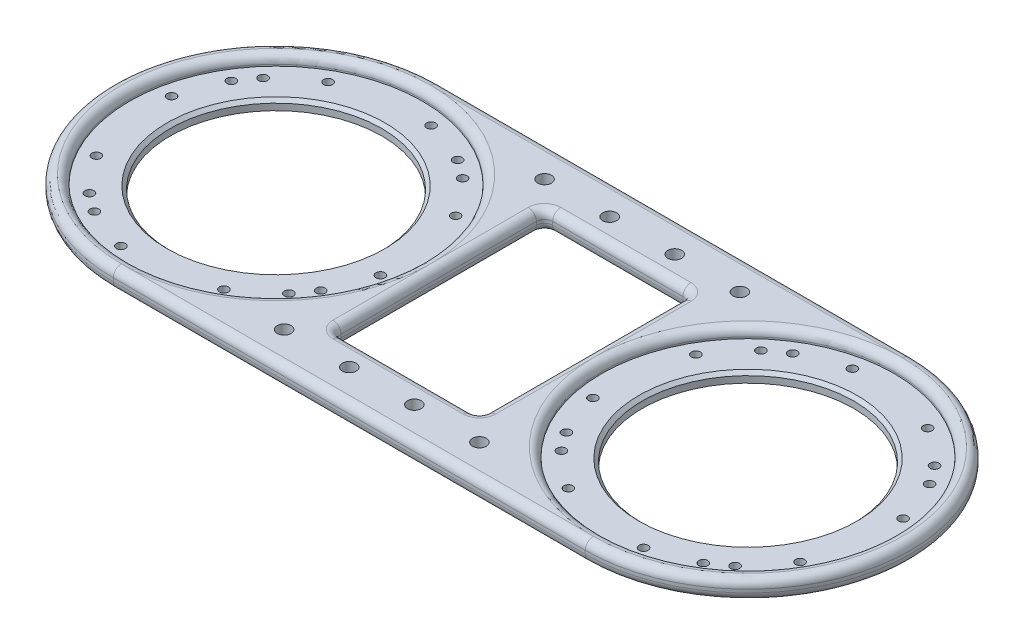
SolidWorks part; units mm, degrees
ref_plane "前视基准面" through (0, 0, 0) normal (0, 0, 1) x (1, 0, 0)
ref_plane "上视基准面" through (0, 0, 0) normal (0, 1, 0) x (1, 0, 0)
ref_plane "右视基准面" through (0, 0, 0) normal (1, 0, 0) x (0, 0, -1)
other "Configuration Table"
sketch "草图1" plane through (0, 0, 0) normal (0, 1, 0) x (1, 0, 0)
  line L0 (-145, 0) -> (145, 0) construction
  line L1 (-145, 100) -> (145, 100)
  line L2 (-145, -100) -> (145, -100)
  arc A0 (-145, 100) -> (-145, -100) centre (-145, 0) ccw
  arc A1 (145, -100) -> (145, 100) centre (145, 0) ccw
  point P3 (0, 0)
  dimension "D1" = 100
  dimension "D2" = 290
extrude "凸台-拉伸1" add sketch "草图1" along normal blind 6 and the other way blind 6
sketch "草图2" plane through (0, 0, 0) normal (0, 0, 1) x (1, 0, 0)
  line L0 (-145, 6) -> (-145, -6) construction
  line L1 (-145, -6) -> (-80, -6)
  line L2 (-145, -6) -> (145, -6) construction
  line L3 (-80, -6) -> (-80, 0)
  line L4 (-80, 0) -> (-55, 0)
  line L5 (-55, 0) -> (-55, 6)
  line L6 (-145, 6) -> (145, 6) construction
  line L7 (-55, 6) -> (-145, 6)
  line L8 (-145, 6) -> (-145, -6)
  dimension "D1" = 130
  dimension "D2" = 180
revolve "切除-旋转1" cut sketch "草图2" angle 360 about L0
sketch "草图3" plane through (0, 0, 0) normal (0, 1, 0) x (1, 0, 0)
  line L0 (-145, 0) -> (-129.4354, 79.7452) construction
  line L1 (-73.8216, 39.1816) -> (-145, 0) construction
  line L2 (-102.9484, 69.5214) -> (-145, 0) construction
  line L3 (-91.648, 61.2791) -> (-145, 0) construction
  line L4 (-145, 0) -> (-145, 81.25) construction
  circle A0 centre (-145, 0) radius 81.25 construction
  circle A1 centre (-102.9484, 69.5214) radius 2.75
  circle A2 centre (-91.648, 61.2791) radius 2.75
  circle A3 centre (-73.8216, 39.1816) radius 2.75
  circle A4 centre (-129.4354, 79.7452) radius 2.75
  circle A5 centre (-145, 0) radius 65 construction
  circle A18 centre (-75.4786, -42.0516) radius 2.75
  circle A19 centre (-83.7209, -53.352) radius 2.75
  circle A20 centre (-105.8184, -71.1784) radius 2.75
  circle A21 centre (-65.2548, -15.5646) radius 2.75
  circle A22 centre (-187.0516, -69.5214) radius 2.75
  circle A23 centre (-198.352, -61.2791) radius 2.75
  circle A24 centre (-216.1784, -39.1816) radius 2.75
  circle A25 centre (-160.5646, -79.7452) radius 2.75
  circle A26 centre (-214.5214, 42.0516) radius 2.75
  circle A27 centre (-206.2791, 53.352) radius 2.75
  circle A28 centre (-184.1816, 71.1784) radius 2.75
  circle A29 centre (-224.7452, 15.5646) radius 2.75
  point P41 (-145, 0)
  dimension "D1" = 162.5
  dimension "D2" = 5.5
  dimension "D3" = 50.124
  dimension "D4" = 20.124
  dimension "D5" = 20.124
  dimension "D6" = 11.044
  dimension "D7" = 4
extrude "切除-拉伸1" cut sketch "草图3" against normal up to next
mirror "镜向1" about plane through (0, 0, 0) normal (1, 0, 0) of "切除-拉伸1", "切除-旋转1"
sketch "草图4" plane through (0, 6, 0) normal (0, 1, 0) x (1, 0, 0)
  line L0 (0, -80) -> (0, -100) construction
  line L1 (-145, -100) -> (145, -100) construction
  line L2 (-64, -100) -> (64, -100)
  arc A0 (0, -80) -> (64, -100) centre (64, 12.4) ccw
  arc A1 (0, -80) -> (-64, -100) centre (-64, 12.4) cw
  dimension "D1" = 20
  dimension "D2" = 64
extrude "切除-拉伸2" [suppressed] cut sketch "草图4" against normal up to next
fillet "圆角1" radius 5 4 edges at (0, -6, -100) (245, -6, 0) (0, -6, 100) (-245, -6, 0)
fillet "圆角2" radius 5 6 edges at (0, 6, -100) (245, 6, 0) (0, 6, 100) (-245, 6, 0) (-145, 6, 90) (145, 6, 90)
chamfer "倒角1" distance 2 angle 45 2 edges at (-145, 0, 65) (145, 0, 65)
sketch "草图5" [suppressed] plane through (0, 0, 0) normal (0, 0, 1) x (1, 0, 0)
  line L0 (-40, 6) -> (40, 6)
  line L1 (64, 6) -> (0, 6) construction
  line L2 (40, 6) -> (25, 86)
  line L3 (25, 86) -> (-25, 86)
  line L4 (0, 86) -> (0, 6) construction
  line L5 (-40, 6) -> (-25, 86)
  dimension "D1" = 80
  dimension "D2" = 50
  dimension "D3" = 80
extrude "凸台-拉伸2" [suppressed] add sketch "草图5" along normal mid plane 90
sketch "草图6" [suppressed] plane through (0, 0, 0) normal (1, 0, 0) x (0, 0, -1)
  line L0 (0, 86) -> (0, 6) construction
  line L1 (-45, 6) -> (45, 6) construction
  line L8 (-45, 86) -> (45, 86) construction
  line L16 (45, 6) -> (45, 86) construction
  line L17 (-39, 6) -> (39, 6)
  line L18 (-39, 6) -> (-39, 86)
  line L19 (-39, 86) -> (39, 86)
  line L20 (39, 6) -> (39, 86)
  line L21 (-39, 6) -> (39, 86) construction
  line L22 (-39, 86) -> (39, 6) construction
  point P5 (0, 6)
  point P6 (0, 46)
  dimension "D1" = 6
extrude "切除-拉伸3" [suppressed] cut sketch "草图6" against normal mid plane 150
sketch "草图7" [suppressed] plane through (0, 0, 0) normal (1, 0, 0) x (0, 0, -1)
  line L0 (-45, 6) -> (45, 6) construction
  line L1 (-45, 6) -> (45, 6) construction
  line L2 (45, 6) -> (95, 6) construction
  line L3 (70, 6) -> (45, 46)
  line L4 (45, 6) -> (45, 86) construction
rib "筋2" [suppressed] sketch "草图7" sketch "草图7" thickness 5 extrusion direction parallel to sketch draft on no parameters "D1"=5
sketch "草图8" [suppressed] plane through (0, 0, 0) normal (1, 0, 0) x (0, 0, -1)
  line L0 (-73.8482, 6) -> (-45, 6) construction
  line L1 (-73.8482, 6) -> (-45, 46)
  line L2 (-45, 6) -> (-45, 86) construction
rib "筋3" [suppressed] sketch "草图8" sketch "草图8" thickness 5 extrusion direction parallel to sketch draft on no parameters "D1"=5
sketch "草图9" [suppressed] plane through (0, 0, 45) normal (0, 0, 1) x (1, 0, 0)
  line L0 (25, 86) -> (-25, 86) construction
  line L1 (-17.5, 78) -> (17.5, 78) construction
  line L2 (-17.5, 78) -> (-17.5, 28) construction
  line L3 (-17.5, 28) -> (17.5, 28) construction
  line L4 (17.5, 78) -> (17.5, 28) construction
  line L5 (0, 86) -> (0, 6) construction
  circle A0 centre (-17.5, 78) radius 4.3
  circle A1 centre (17.5, 78) radius 4.3
  circle A2 centre (17.5, 28) radius 4.3
  circle A3 centre (-17.5, 28) radius 4.3
  point P9 (0, 78)
  dimension "D2" = 8.6
  dimension "D1" = 8
  dimension "D3" = 35
  dimension "D4" = 50
extrude "切除-拉伸4" [suppressed] cut sketch "草图9" against normal up to surface (90 mm away)
fillet "圆角4" [suppressed] radius 8
fillet "圆角5" [suppressed] radius 6
fillet "圆角6" [suppressed] radius 6
sketch "草图10" [suppressed] plane through (0, 6, 0) normal (0, 1, 0) x (1, 0, 0)
  line L0 (-45.08, 25) -> (45.08, 25)
  line L1 (46.6394, 31) -> (-46.6394, 31) construction
  line L2 (45.08, -25) -> (-45.08, -25)
  line L3 (-42, 0) -> (42, 0) construction
  arc A0 (45.08, 25) -> (45.08, -25) centre (145, 0) ccw
  arc A1 (-45.08, -25) -> (-45.08, 25) centre (-145, 0) ccw
  circle A2 centre (145, 0) radius 95 construction
  dimension "D1" = 8
  dimension "D2" = 6
extrude "切除-拉伸5" [suppressed] cut sketch "草图10" against normal up to next
fillet "圆角7" [suppressed] radius 5
sketch "草图11" plane through (0, 6, 0) normal (0, 1, 0) x (1, 0, 0)
  line L0 (-275.0843, 0) -> (287.0305, 0) construction
  line L1 (0, 0) -> (0, 187.1026) construction
  line L2 (-45, 65) -> (45, 65)
  line L3 (-45, 65) -> (-45, -65)
  line L4 (-45, -65) -> (45, -65)
  line L5 (45, 65) -> (45, -65)
  dimension "D1" = 90
  dimension "D2" = 130
extrude "切除-拉伸6" cut sketch "草图11" against normal blind 47
fillet "圆角8" radius 5 12 edges at (-45, -6, 0) (0, -6, 65) (0, -6, -65) (45, -6, 0) (45, 0, -65) (-45, 0, -65) (45, 0, 65) (-45, 0, 65) (0, 6, 65) (45, 6, 0) (-45, 6, 0) (0, 6, -65)
sketch "草图12" plane through (0, 6, 0) normal (0, 1, 0) x (1, 0, 0)
  line L0 (-265.7211, 0) -> (250.8692, 0) construction
  line L1 (0, 152.8784) -> (0, -181.2909) construction
  circle A1 centre (60, -80) radius 4.25
  circle A2 centre (20, -80) radius 4.25
  circle A3 centre (-20, -80) radius 4.25
  circle A4 centre (-60, -80) radius 4.25
  circle A5 centre (20, 80) radius 4.25
  circle A6 centre (60, 80) radius 4.25
  circle A7 centre (-60, 80) radius 4.25
  circle A8 centre (-20, 80) radius 4.25
  point P9 (0, 0)
  dimension "D1" = 8.5
  dimension "D2" = 80
  dimension "D3" = 20
  dimension "D4" = 40
extrude "切除-拉伸7" cut sketch "草图12" against normal blind 47
